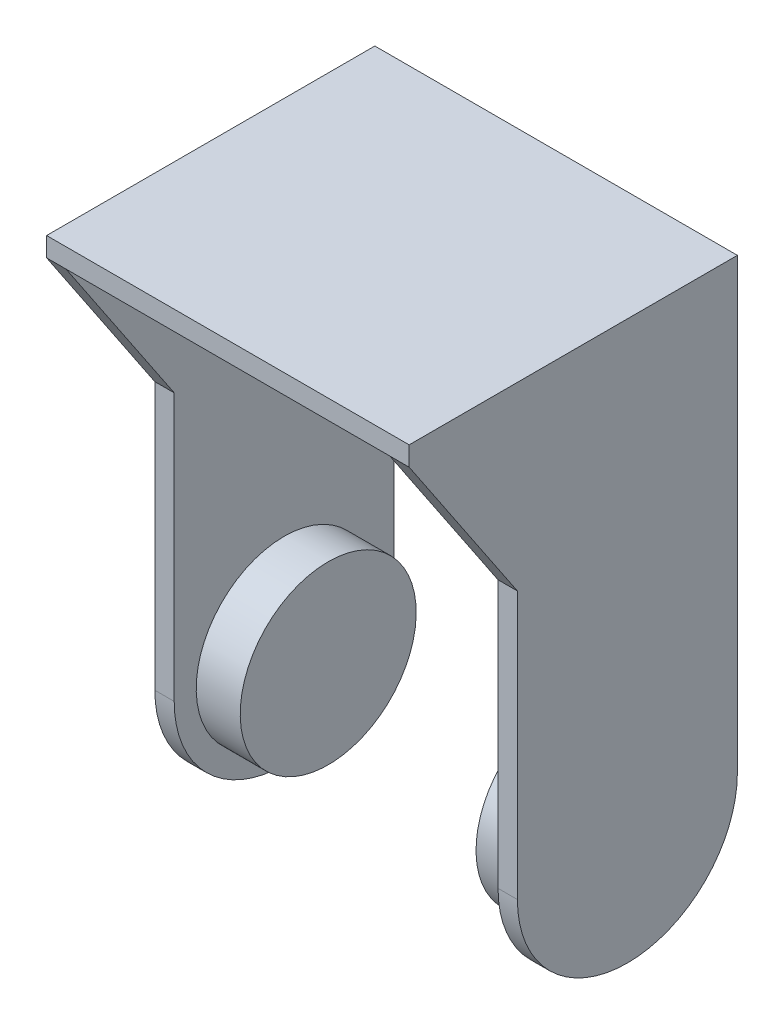
SolidWorks part; units mm, degrees
ref_plane "Front Plane" through (0, 0, 0) normal (0, 0, 1) x (1, 0, 0)
ref_plane "Top Plane" through (0, 0, 0) normal (0, 1, 0) x (1, 0, 0)
ref_plane "Right Plane" through (0, 0, 0) normal (1, 0, 0) x (0, 0, -1)
sketch "Sketch1" plane through (0, 0, 0) normal (0, 0, 1) x (1, 0, 0)
  line L0 (0, 0) -> (0, 63.4)
  line L1 (0, 63.4) -> (41.2, 63.4)
  line L2 (41.2, 63.4) -> (41.2, 0)
  line L3 (41.2, 0) -> (39, 0)
  line L4 (39, 0) -> (39, 61.2)
  line L5 (39, 61.2) -> (2.2, 61.2)
  line L6 (2.2, 61.2) -> (2.2, 0)
  line L7 (2.2, 0) -> (0, 0)
  dimension "D1" = 63.4
  dimension "D2" = 41.2
  dimension "D3" = 2.2
  dimension "D4" = 2.2
  dimension "D5" = 2.2
sketch "Sketch2" plane through (0, 0, 0) normal (1, 0, 0) x (0, 0, -1)
  line L0 (0, 0) -> (-25, 0)
  line L1 (-25, 0) -> (-25, 42.8671)
  line L2 (-25, 42.8671) -> (-37.3, 61.2)
  line L3 (-37.3, 61.2) -> (-37.3, 63.4)
  line L4 (-37.3, 63.4) -> (0, 63.4)
  line L5 (0, 63.4) -> (0, 0) construction
  line L6 (0, 0) -> (0, 63.4) construction
  line L7 (0, 63.4) -> (0, 0)
  dimension "D1" = 37.3
  dimension "D2" = 25
  dimension "D3" = 2.2
extrude "Boss-Extrude1" add sketch "Sketch2" along normal up to vertex (41.2 mm away) contours L4 L7 L0 L1 L2 L3 up to point (41.2, 63.4, 0)
sketch "Sketch4" plane through (0, 0, 0) normal (0, 0, 1) x (1, 0, 0)
  line L0 (2.2, 61.2) -> (2.2, 0)
  line L1 (2.2, 0) -> (39, 0)
  line L2 (39, 0) -> (39, 61.2)
  line L3 (39, 61.2) -> (2.2, 61.2)
extrude "Cut-Extrude1" cut sketch "Sketch4" along normal blind 10000
sketch "Sketch5" plane through (2.2, 0, 0) normal (1, 0, 0) x (0, 0, -1)
  circle A0 centre (-12.5, 12.5) radius 12.5
  circle A1 centre (-12.5, 12.5) radius 10
extrude "Boss-Extrude2" add sketch "Sketch5" along normal blind 5 contours A1
ref_plane "Plane1" through (20.6, 0, 0) normal (1, 0, 0) x (0, 0, -1)
mirror "Mirror1" about plane through (20.6, 0, 0) normal (1, 0, 0) of "Boss-Extrude2"
fillet "Fillet1" radius 12.5 4 edges at (1.1, 0, 25) (1.1, 0, 0) (40.1, 0, 0) (40.1, 0, 25)
